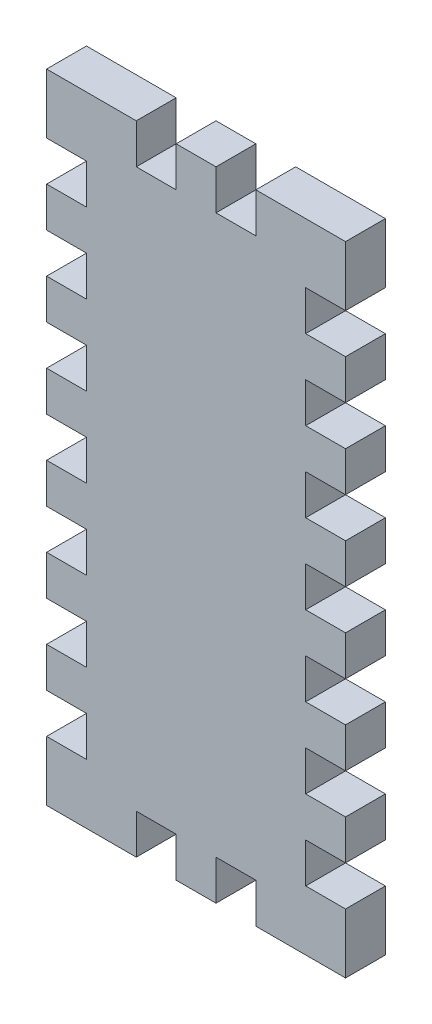
SolidWorks part; units mm, degrees
ref_plane "Front Plane" through (0, 0, 0) normal (0, 0, 1) x (1, 0, 0)
ref_plane "Top Plane" through (0, 0, 0) normal (0, 1, 0) x (1, 0, 0)
ref_plane "Right Plane" through (0, 0, 0) normal (1, 0, 0) x (0, 0, -1)
sketch "Sketch1" plane through (0, 0, 0) normal (0, 0, 1) x (1, 0, 0)
  line L1 (0, -170.3451) -> (-47.625, -170.3451)
  line L2 (0, -170.3451) -> (0, -68.7451)
  line L3 (0, -68.7451) -> (-47.625, -68.7451)
  line L4 (-47.625, -170.3451) -> (-47.625, -68.7451)
  dimension "D1" = 101.6
extrude "Boss-Extrude1" add sketch "Sketch1" against normal blind 6.35 contours L1 L4 L3 L2
sketch "Sketch3" plane through (0, 0, 0) normal (0, 0, 1) x (1, 0, 0)
  line L0 (-30.1625, -68.7451) -> (-17.4625, -68.7451) construction
  line L1 (0, -68.7451) -> (-47.625, -68.7451) construction
  line L2 (0, -170.3451) -> (-47.625, -170.3451) construction
  line L3 (-20.6375, -75.0951) -> (-14.2875, -75.0951)
  line L4 (-20.6375, -75.0951) -> (-20.6375, -62.3951)
  line L5 (-20.6375, -62.3951) -> (-14.2875, -62.3951)
  line L6 (-14.2875, -75.0951) -> (-14.2875, -62.3951)
  line L7 (-20.6375, -75.0951) -> (-14.2875, -62.3951) construction
  line L8 (-20.6375, -62.3951) -> (-14.2875, -75.0951) construction
  line L9 (-33.3375, -75.0951) -> (-26.9875, -75.0951)
  line L10 (-33.3375, -75.0951) -> (-33.3375, -62.3951)
  line L11 (-33.3375, -62.3951) -> (-26.9875, -62.3951)
  line L12 (-26.9875, -75.0951) -> (-26.9875, -62.3951)
  line L13 (-33.3375, -75.0951) -> (-26.9875, -62.3951) construction
  line L14 (-33.3375, -62.3951) -> (-26.9875, -75.0951) construction
  line L15 (-26.9875, -163.9951) -> (-33.3375, -163.9951)
  line L16 (-26.9875, -163.9951) -> (-26.9875, -176.6951)
  line L17 (-26.9875, -176.6951) -> (-33.3375, -176.6951)
  line L18 (-33.3375, -163.9951) -> (-33.3375, -176.6951)
  line L19 (-26.9875, -163.9951) -> (-33.3375, -176.6951) construction
  line L20 (-26.9875, -176.6951) -> (-33.3375, -163.9951) construction
  line L22 (-20.6375, -163.9951) -> (-14.2875, -163.9951)
  line L23 (-20.6375, -163.9951) -> (-20.6375, -176.6951)
  line L24 (-20.6375, -176.6951) -> (-14.2875, -176.6951)
  line L25 (-14.2875, -163.9951) -> (-14.2875, -176.6951)
  line L26 (-20.6375, -163.9951) -> (-14.2875, -176.6951) construction
  line L27 (-20.6375, -176.6951) -> (-14.2875, -163.9951) construction
  point P2 (-23.8125, -68.7451)
  point P13 (-30.1625, -170.3451)
  point P20 (-17.4625, -170.3451)
  dimension "D1" = 12.7
  dimension "D2" = 6.35
  dimension "D3" = 12.7
sketch "Sketch4" plane through (0, 0, 0) normal (0, 0, 1) x (1, 0, 0)
  line L0 (6.35, -122.7201) -> (-6.35, -116.3701) construction
  line L1 (6.35, -116.3701) -> (-6.35, -116.3701)
  line L2 (6.35, -116.3701) -> (6.35, -122.7201)
  line L3 (6.35, -122.7201) -> (-6.35, -122.7201)
  line L4 (-6.35, -116.3701) -> (-6.35, -122.7201)
  line L5 (-53.975, -116.3701) -> (-41.275, -116.3701)
  line L6 (-53.975, -116.3701) -> (-53.975, -122.7201)
  line L7 (-53.975, -122.7201) -> (-41.275, -122.7201)
  line L8 (-41.275, -116.3701) -> (-41.275, -122.7201)
  line L9 (0, -170.3451) -> (0, -68.7451) construction
  point P4 (0, -119.5451)
  dimension "D1" = 12.7
  dimension "D2" = 6.35
extrude "Cut-Extrude1" cut sketch "Sketch4" against normal through all
pattern_linear "LPattern1" count 4 spacing 12.7 along (0, -1, 0) count 4 spacing 12.7 along (0, 1, 0) of "Cut-Extrude1"
sketch "Sketch5" plane through (0, 0, 0) normal (0, 0, 1) x (1, 0, 0)
  line L1 (-23.8125, -160.8201) -> (-23.8125, -78.2701) construction
  line L2 (-23.8125, -138.5951) -> (-23.8125, -183.0451) construction
  line L3 (-15.875, -138.5951) -> (-15.875, -183.0451)
  line L4 (-31.75, -138.5951) -> (-31.75, -183.0451)
  line L5 (-23.8125, -100.4951) -> (-23.8125, -56.0451) construction
  line L6 (-31.75, -100.4951) -> (-31.75, -56.0451)
  line L7 (-15.875, -100.4951) -> (-15.875, -56.0451)
  arc A0 (-15.875, -138.5951) -> (-31.75, -138.5951) centre (-23.8125, -138.5951) ccw
  arc A1 (-31.75, -183.0451) -> (-15.875, -183.0451) centre (-23.8125, -183.0451) ccw
  arc A2 (-31.75, -100.4951) -> (-15.875, -100.4951) centre (-23.8125, -100.4951) ccw
  arc A3 (-15.875, -56.0451) -> (-31.75, -56.0451) centre (-23.8125, -56.0451) ccw
  point P6 (-23.8125, -119.5451)
  point P9 (-23.8125, -160.8201)
  point P16 (-23.8125, -78.2701)
  dimension "D2" = 44.45
  dimension "D3" = 7.9375
  dimension "D1" = 82.55
extrude "Weight savings" [suppressed] cut sketch "Sketch5" against normal through all
sketch "Sketch6" plane through (0, 0, -6.35) normal (0, 0, -1) x (-1, 0, 0)
  line L2 (30.1625, -152.8826) -> (17.4625, -152.8826)
  line L3 (30.1625, -152.8826) -> (30.1625, -146.5326)
  line L4 (30.1625, -146.5326) -> (17.4625, -146.5326)
  line L5 (17.4625, -152.8826) -> (17.4625, -146.5326)
  line L6 (30.1625, -152.8826) -> (17.4625, -146.5326) construction
  line L7 (30.1625, -146.5326) -> (17.4625, -152.8826) construction
  point P4 (23.8125, -149.7076)
  dimension "D1" = 6.35
  dimension "D2" = 12.7
extrude "Center Panel Mate" [suppressed] cut sketch "Sketch6" against normal through all
extrude "Cut-Extrude2" cut sketch "Sketch3" against normal through all
